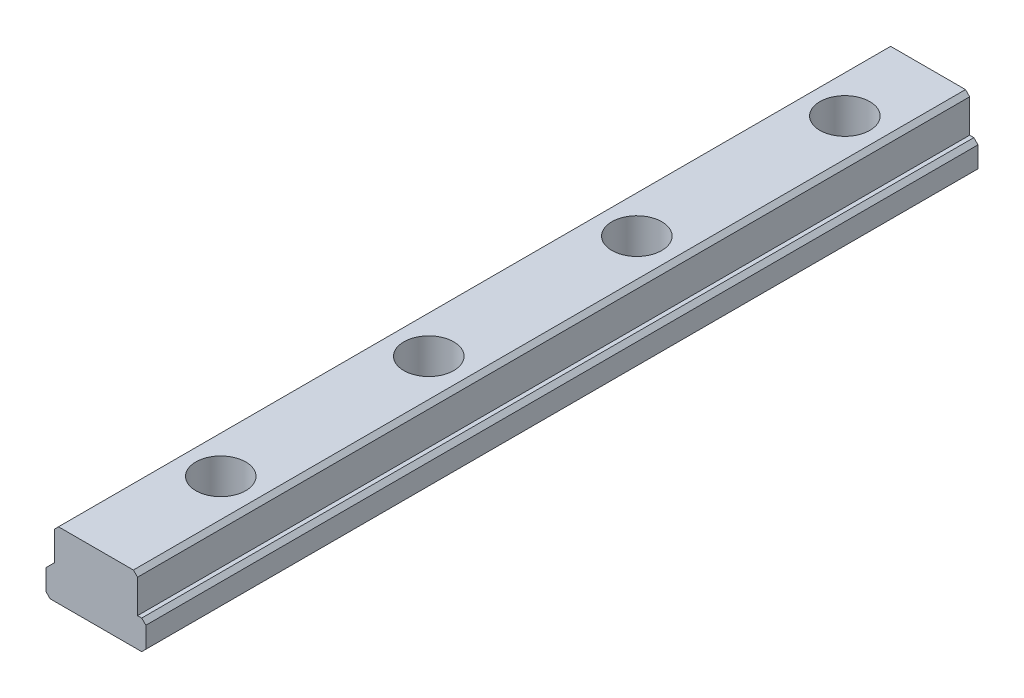
SolidWorks part; units mm, degrees
ref_plane "前视基准面" through (0, 0, 0) normal (0, 0, 1) x (1, 0, 0)
ref_plane "上视基准面" through (0, 0, 0) normal (0, 1, 0) x (1, 0, 0)
ref_plane "右视基准面" through (0, 0, 0) normal (1, 0, 0) x (0, 0, -1)
sketch "草图1" plane through (0, 0, 0) normal (0, 0, 1) x (1, 0, 0)
  line L0 (-8.1097, 0) -> (9.8454, 0) construction
  line L1 (-6, 4) -> (-6, -4)
  line L2 (-6, -4) -> (6, -4)
  line L3 (6, -4) -> (6, 4)
  line L4 (6, 4) -> (-6, 4)
  dimension "D1" = 12
  dimension "D2" = 8
  dimension "D3" = 4
  dimension "D4" = 6
extrude "凸台-拉伸1" add sketch "草图1" along normal blind 100
sketch "草图2" plane through (0, 0, 100) normal (0, 0, 1) x (1, 0, 0)
  line L0 (0, 4) -> (0, -4) construction
  line L1 (6, 4) -> (-6, 4) construction
  line L2 (-6, -4) -> (6, -4) construction
  line L3 (-6, 4) -> (-6, -0.5)
  line L4 (-6, 4) -> (-6, -4) construction
  line L5 (-6, -0.5) -> (-5, -0.5)
  line L6 (-5, -0.5) -> (-5, 4)
  line L7 (-5, 4) -> (-6, 4)
  line L8 (6, -0.5) -> (5, -0.5)
  line L9 (5, 4) -> (6, 4)
  line L10 (5, -0.5) -> (5, 4)
  line L11 (6, 4) -> (6, -0.5)
  dimension "D1" = 4.5
  dimension "D2" = 1
extrude "切除-拉伸1" cut sketch "草图2" against normal blind 400
chamfer "倒角1" distance 0.5 angle 45 7 edges at (-6, -0.5, 50) (-6, -4, 50) (6, -4, 50) (6, -0.5, 50) (5, 4, 50) (-5, -0.5, 50) (-5, 4, 50)
sketch "草图3" plane through (0, 4, 0) normal (0, 1, 0) x (1, 0, 0)
  line L0 (4.5, 0) -> (-4.5, 0) construction
  line L1 (6, 0) -> (6, -100) construction
  circle A0 centre (0, -10) radius 1.75
  circle A1 centre (0, -35) radius 1.75
  circle A2 centre (0, -60) radius 1.75
  circle A3 centre (0, -85) radius 1.75
  circle A4 centre (0, -110) radius 1.75
  circle A5 centre (0, -135) radius 1.75
  circle A6 centre (0, -160) radius 1.75
  circle A7 centre (0, -185) radius 1.75
  circle A8 centre (0, -210) radius 1.75
  circle A9 centre (0, -235) radius 1.75
  circle A10 centre (0, -260) radius 1.75
  circle A11 centre (0, -285) radius 1.75
  circle A12 centre (0, -310) radius 1.75
  circle A13 centre (0, -335) radius 1.75
  circle A14 centre (0, -360) radius 1.75
  circle A15 centre (0, -385) radius 1.75
  dimension "D1" = 3.5
  dimension "D2" = 10
  dimension "D3" = 6
  dimension "D4" = 16
extrude "切除-拉伸2" cut sketch "草图3" against normal blind 400
sketch "草图4" plane through (0, 4, 0) normal (0, 1, 0) x (1, 0, 0)
  circle A0 centre (0, -10) radius 3
  circle A1 centre (0, -35) radius 3
  circle A2 centre (0, -60) radius 3
  circle A3 centre (0, -85) radius 3
  circle A4 centre (0, -110) radius 3
  circle A5 centre (0, -135) radius 3
  circle A6 centre (0, -160) radius 3
  circle A7 centre (0, -185) radius 3
  circle A8 centre (0, -210) radius 3
  circle A9 centre (0, -235) radius 3
  circle A10 centre (0, -260) radius 3
  circle A11 centre (0, -285) radius 3
  circle A12 centre (0, -310) radius 3
  circle A13 centre (0, -335) radius 3
  circle A14 centre (0, -360) radius 3
  circle A15 centre (0, -385) radius 3
  dimension "D1" = 6
  dimension "D2" = 16
extrude "切除-拉伸3" cut sketch "草图4" against normal blind 4.5
